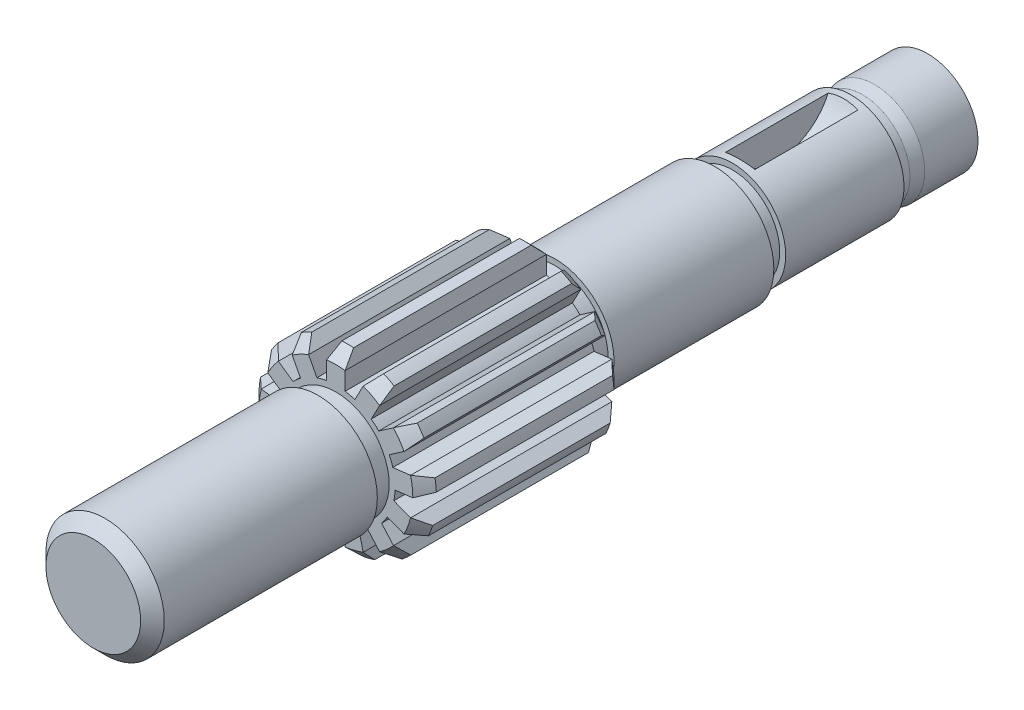
SolidWorks part; units mm, degrees
ref_plane "Спереди" through (0, 0, 0) normal (0, 0, 1) x (1, 0, 0)
ref_plane "Сверху" through (0, 0, 0) normal (0, 1, 0) x (1, 0, 0)
ref_plane "Справа" through (0, 0, 0) normal (1, 0, 0) x (0, 0, -1)
other "Configuration Table"
sketch "Эскиз1" plane through (0, 0, 0) normal (1, 0, 0) x (0, 0, -1)
  line L0 (-57.4482, 0) -> (84.5518, 0) construction
  line L1 (84.5518, 0) -> (84.5518, 7)
  line L4 (84.5518, 7) -> (83.5518, 8.5)
  line L5 (83.5518, 8.5) -> (74.5518, 8.5)
  line L6 (72.5518, 8) -> (70.5518, 8)
  line L7 (70.5518, 8) -> (70.5518, 9)
  line L8 (74.5518, 8.5) -> (72.5518, 8)
  line L9 (70.5518, 9) -> (50.5518, 9)
  line L10 (50.5518, 9) -> (50.5518, 8)
  line L11 (50.5518, 8) -> (47.5518, 8)
  line L12 (47.5518, 8) -> (47.5518, 10)
  line L13 (47.5518, 10) -> (20.5518, 10)
  line L14 (20.5518, 10) -> (20.5518, 9)
  line L15 (20.5518, 9) -> (17.5518, 9)
  line L16 (17.5518, 9) -> (17.5518, 10)
  line L17 (17.5518, 10) -> (-16.4482, 10)
  line L18 (-16.4482, 10) -> (-16.4482, 9)
  line L19 (-16.4482, 9) -> (-19.4482, 9)
  line L20 (-57.4482, 0) -> (-57.4482, 8)
  line L21 (-57.4482, 8) -> (-55.4482, 10)
  line L22 (-55.4482, 10) -> (-19.4482, 10)
  line L23 (-19.4482, 10) -> (-19.4482, 9)
  line L24 (-57.4482, 0) -> (84.5518, 0)
  dimension "D1" = 142
  dimension "D2" = 7
  dimension "D3" = 8.5
  dimension "D4" = 9
  dimension "D5" = 2
  dimension "D6" = 8
  dimension "D7" = 2
  dimension "D8" = 9
  dimension "D9" = 20
  dimension "D10" = 8
  dimension "D11" = 3
  dimension "D12" = 10
  dimension "D13" = 27
  dimension "D14" = 1
  dimension "D15" = 3
  dimension "D16" = 34
  dimension "D17" = 3
  dimension "D18" = 8
  dimension "D19" = 36
  dimension "D20" = 10
  dimension "D21" = 2
  dimension "D22" = 57.4482
  dimension "D23" = 9
revolve "Повернуть1" add sketch "Эскиз1" angle 360 about L0
cosmetic thread "Условное изображение резьбы1" parameters "D2"=14
ref_plane "Плоскость1" through (0, 0, 0.4482) normal (0, 0, 1) x (1, 0, 0)
sketch "Эскиз2" plane through (0, 0, 0.4482) normal (0, 0, 1) x (1, 0, 0)
  line L0 (1.567, 12.9052) -> (0.9938, 14.967)
  line L1 (-1.567, 12.9052) -> (-0.9938, 14.967)
  line L2 (1.567, 12.9052) -> (1.567, 9.8765)
  line L3 (-1.567, 12.9052) -> (-1.567, 9.8765)
  circle A0 centre (0, 0) radius 13 construction
  circle A1 centre (0, 0) radius 15 construction
  arc A3 (1.567, 12.9052) -> (-1.567, 12.9052) centre (0, 0) ccw construction
  arc A8 (0.9938, 14.967) -> (-0.9938, 14.967) centre (0, 0) ccw
  circle A9 centre (0, 0) radius 10 construction
  arc A10 (1.567, 9.8765) -> (-1.567, 9.8765) centre (0, 0) ccw
  point P7 (0, 13)
  point P115 (0, 0)
  dimension "D1" = 3.1416
  dimension "D2" = 26
  dimension "D3" = 30
  dimension "D6" = 1.9891
extrude "Бобышка-Вытянуть1" add sketch "Эскиз2" along normal blind 16 and the other way blind 18 contours L0 A8 L1 L3 A10 L2
chamfer "Фаска1" distance 2 angle 45 2 edges at (0, 15, 16.4482) (0, 15, -17.5518)
pattern_circular "Круговой массив1" count 13 over 360 about axis through (0, 0, 57.4482) along (0, 0, 1) of "Фаска1", "Бобышка-Вытянуть1"
sketch "Эскиз3" plane through (0, 0, 0) normal (1, 0, 0) x (0, 0, -1)
  line L1 (60.5518, 10.5) -> (60.5518, 3) construction
  line L4 (51.2647, 10.5) -> (69.8388, 10.5)
  arc A0 (51.2647, 10.5) -> (69.8388, 10.5) centre (60.5518, 12.5) ccw
  dimension "D2" = 9.5
  dimension "D1" = 18.5742
  dimension "D3" = 51.2647
  dimension "D4" = 10.5
extrude "Вырез-Вытянуть1" cut sketch "Эскиз3" against normal mid plane 5
